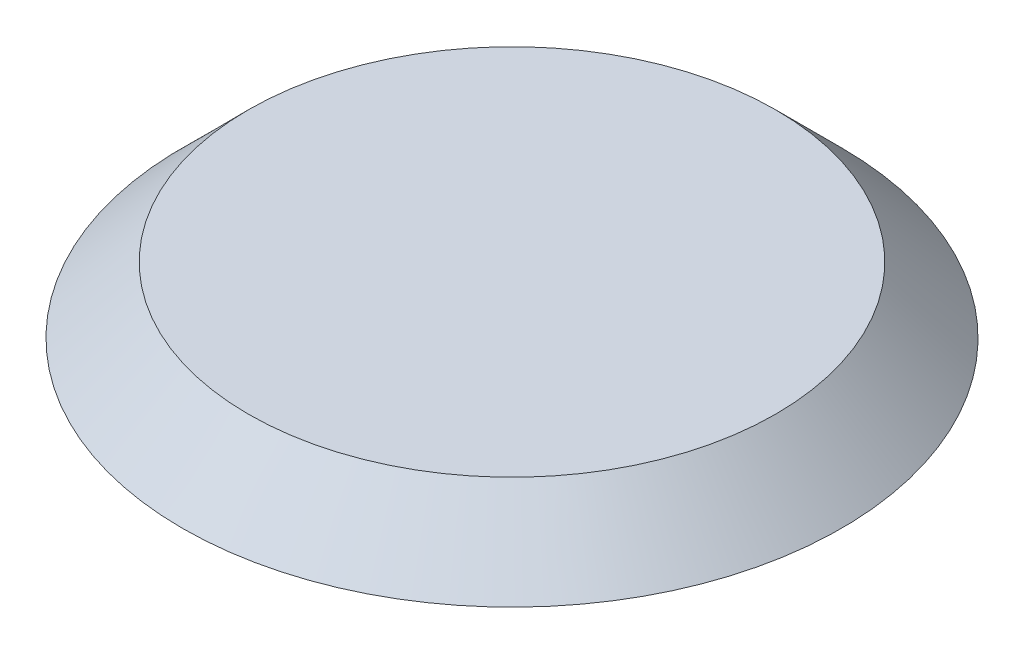
SolidWorks part; units mm, degrees
ref_plane "Plan de face" through (0, 0, 0) normal (0, 0, 1) x (1, 0, 0)
ref_plane "Plan de dessus" through (0, 0, 0) normal (0, 1, 0) x (1, 0, 0)
ref_plane "Plan de droite" through (0, 0, 0) normal (1, 0, 0) x (0, 0, -1)
sketch "Esquisse1" plane through (0, 0, 0) normal (0, 1, 0) x (1, 0, 0)
  circle A0 centre (0, 0) radius 15
extrude "Boss.-Extru.1" add sketch "Esquisse1" along normal blind 3
chamfer "Chanfrein1" distance 3 angle 45 1 edges at (0, 3, 15)
sketch "Esquisse2" plane through (0, 3, 0) normal (0, 1, 0) x (1, 0, 0)
  circle A1 centre (0, 0) radius 12
  circle A2 centre (0, 0) radius 12
  dimension "D1" = 0
